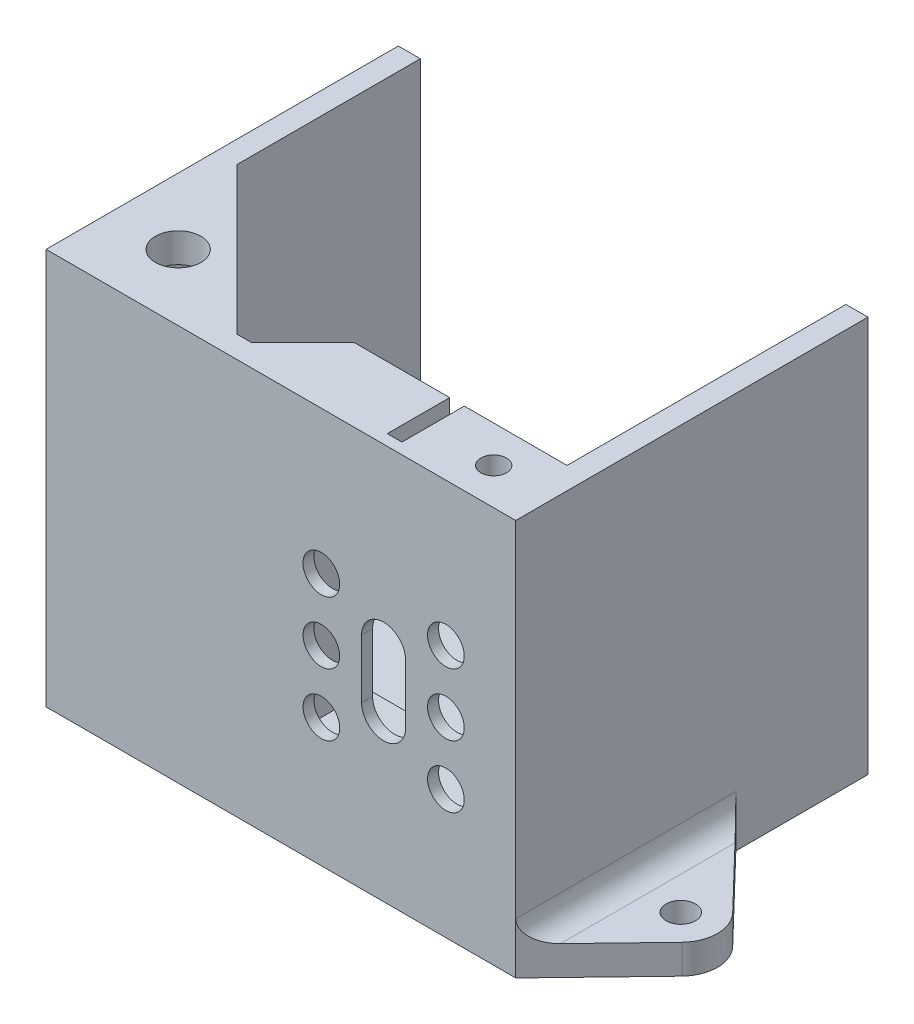
SolidWorks part; units mm, degrees
ref_plane "Płaszczyzna przednia" through (0, 0, 0) normal (0, 0, 1) x (1, 0, 0)
ref_plane "Płaszczyzna górna" through (0, 0, 0) normal (0, 1, 0) x (1, 0, 0)
ref_plane "Płaszczyzna prawa" through (0, 0, 0) normal (1, 0, 0) x (0, 0, -1)
sketch "Sketch1" plane through (0, 0, 0) normal (0, 1, 0) x (1, 0, 0)
  line L1 (-32, 24) -> (32, 24)
  line L2 (-32, 24) -> (-32, -24)
  line L3 (-32, -24) -> (32, -24)
  line L4 (32, 24) -> (32, -24)
  line L5 (-32, 24) -> (32, -24) construction
  line L6 (-32, -24) -> (32, 24) construction
  point P0 (0, 0)
  dimension "D1" = 64
  dimension "D2" = 48
extrude "Boss-Extrude1" add sketch "Sketch1" along normal blind 4
sketch "Sketch2" plane through (0, 0, 0) normal (0, -1, 0) x (1, 0, 0)
  line L9 (-20.6514, -16) -> (-22.3257, -13.1)
  line L10 (-22.3257, -13.1) -> (-25.6743, -13.1)
  line L11 (-25.6743, -13.1) -> (-27.3486, -16)
  line L12 (-27.3486, -16) -> (-25.6743, -18.9)
  line L13 (-25.6743, -18.9) -> (-22.3257, -18.9)
  line L14 (-22.3257, -18.9) -> (-20.6514, -16)
  line L15 (-32, -24) -> (-32, 24) construction
  line L16 (32, -24) -> (-32, -24) construction
  circle A0 centre (-24, -16) radius 2.9 construction
  dimension "D3" = 5.8
  dimension "D1" = 8
  dimension "D2" = 8
extrude "Cut-Extrude1" cut sketch "Sketch2" against normal blind 2.4
sketch "Sketch4" plane through (0, 0, 0) normal (0, -1, 0) x (1, 0, 0)
  line L0 (-32, -24) -> (-32, 24) construction
  line L1 (9.3486, 10) -> (7.6743, 12.9)
  line L2 (7.6743, 12.9) -> (4.3257, 12.9)
  line L3 (4.3257, 12.9) -> (2.6514, 10)
  line L4 (2.6514, 10) -> (4.3257, 7.1)
  line L5 (4.3257, 7.1) -> (7.6743, 7.1)
  line L6 (7.6743, 7.1) -> (9.3486, 10)
  line L8 (32, -24) -> (-32, -24) construction
  circle A0 centre (6, 10) radius 2.9 construction
  dimension "D3" = 5.8
  dimension "D1" = 38
  dimension "D2" = 34
extrude "Cut-Extrude2" cut sketch "Sketch4" against normal blind 2.4
sketch "Sketch6" plane through (0, 4, 0) normal (0, 1, 0) x (1, 0, 0)
  line L0 (-29, 21) -> (-29, 24)
  line L1 (-32, 24) -> (32, 24)
  line L2 (-32, 24) -> (-32, -24)
  line L3 (-32, -24) -> (32, -24)
  line L4 (32, 24) -> (32, -24)
  line L5 (-29, 21) -> (29, 21)
  line L6 (-29, 21) -> (-29, -21)
  line L7 (-29, -21) -> (29, -21)
  line L8 (29, 21) -> (29, -21)
  line L9 (-29, 21) -> (29, -21) construction
  line L10 (-29, -21) -> (29, 21) construction
  line L11 (29, 21) -> (29, 24)
  point P6 (0, 0)
  line M1 (32, -24) -> (32, 24)
  line M2 (32, 24) -> (-32, 24)
  line M3 (-32, 24) -> (-32, -24)
  line M4 (-32, -24) -> (32, -24)
  dimension "D1" = 58
  dimension "D2" = 42
extrude "Boss-Extrude3" add sketch "Sketch6" along normal blind 50 contours L11 L8 L7 L6 L0 M2 M3 M4 M1 region at (-29.8, 4, 0)
sketch "Sketch9" plane through (0, 4, 0) normal (0, 1, 0) x (1, 0, 0)
  line L0 (1, -13) -> (-7, -21)
  line L3 (29, -13) -> (1, -13)
  line L5 (-29, -21) -> (29, -21) construction
  line L6 (-7, -21) -> (29, -21)
  line L7 (1, -13) -> (-7, -21)
  line L9 (29, -21) -> (29, -13)
  line M3 (29, -21) -> (29, 24)
  line M6 (-29, -21) -> (29, -21)
  dimension "D1" = 8
  dimension "D2" = 8
  dimension "D3" = 28
extrude "Boss-Extrude4" add sketch "Sketch9" along normal blind 50 contours L3 L0 M3 M6 region at (12.9167, 4, 17.1667)
sketch "Sketch10" plane through (0, 0, 13) normal (0, 0, -1) x (-1, 0, 0)
  line L0 (-29, 54) -> (-29, 4) construction
  line L1 (-27, 39) -> (-1, 39)
  line L2 (-27, 39) -> (-27, 13)
  line L3 (-27, 13) -> (-1, 13)
  line L4 (-1, 39) -> (-1, 13)
  line L5 (-27, 39) -> (-1, 13) construction
  line L6 (-27, 13) -> (-1, 39) construction
  line L7 (-14, 39) -> (-14, 54) construction
  line L9 (-29, 54) -> (-1, 54) construction
  line L15 (-14.9986, 39) -> (-13.0014, 39)
  line L16 (-14.9986, 39) -> (-14.9986, 54)
  line L17 (-14.9986, 54) -> (-13.0014, 54)
  line L18 (-13.0014, 39) -> (-13.0014, 54)
  line L19 (-14.9986, 39) -> (-13.0014, 54) construction
  line L20 (-14.9986, 54) -> (-13.0014, 39) construction
  point P0 (-14, 26)
  point P9 (-14, 46.5)
  line M4 (-1, 4) -> (-1, 54)
  line M5 (-1, 54) -> (-29, 54)
  dimension "D1" = 26
  dimension "D2" = 26
  dimension "D3" = 15
  dimension "D5" = 28
extrude "Cut-Extrude4" cut sketch "Sketch10" against normal blind 9.5 contours L2 L3 L1 M4 | L1 M5 region at (14, 26, 13) region at (14, 46.5, 13)
sketch "Sketch13" plane through (0, 54, 0) normal (0, 1, 0) x (1, 0, 0)
  line L1 (29, -13) -> (-7.9463, -13)
  line L2 (29, -13) -> (29, -14)
  line L3 (29, -14) -> (-7.9463, -14)
  line L4 (-7.9463, -13) -> (-7.9463, -14)
  dimension "D1" = 1
extrude "Cut-Extrude6" cut sketch "Sketch13" against normal blind 32
sketch "Sketch15" plane through (0, 54, 0) normal (0, 1, 0) x (1, 0, 0)
  line L0 (-29, -1) -> (-9, -21)
  line L5 (-29, 24) -> (-29, -21) construction
  line L6 (-29, -21) -> (-7, -21) construction
  line L7 (-29, 24) -> (-29, -21) construction
  line L8 (-29, -1) -> (-29, -21)
  line L9 (-29, -21) -> (-9, -21)
  line L10 (-32, 24) -> (-32, -24) construction
  line L11 (-32, -24) -> (32, -24) construction
  circle A0 centre (-23, -15) radius 3.1
  dimension "D3" = 9
  dimension "D1" = 20
  dimension "D2" = 20
  dimension "D4" = 9
extrude "Boss-Extrude5" add sketch "Sketch15" against normal blind 4
sketch "Sketch17" plane through (0, 54, 0) normal (0, 1, 0) x (1, 0, 0)
  line L0 (32, -24) -> (32, 24) construction
  line L7 (-32, -24) -> (32, -24) construction
  line L8 (24, -19) -> (24, -24) construction
  line L9 (24, -19) -> (32, -19) construction
  line L11 (24, -15.6514) -> (21.1, -17.3257)
  line L12 (21.1, -17.3257) -> (21.1, -20.6743)
  line L13 (21.1, -20.6743) -> (24, -22.3486)
  line L14 (24, -22.3486) -> (26.9, -20.6743)
  line L15 (26.9, -20.6743) -> (26.9, -17.3257)
  line L16 (26.9, -17.3257) -> (24, -15.6514)
  circle A0 centre (24, -19) radius 2.9 construction
  dimension "D1" = 8
  dimension "D3" = 5.8
  dimension "D2" = 5
extrude "Cut-Extrude7" cut sketch "Sketch17" against normal blind 7
sketch "Sketch18" plane through (0, 0, 14) normal (0, 0, -1) x (-1, 0, 0)
  line L0 (-14.9986, 54) -> (-29, 54) construction
  line L1 (-26.9, 49.6) -> (-21.1, 49.6)
  line L2 (-26.9, 49.6) -> (-26.9, 47)
  line L3 (-26.9, 47) -> (-21.1, 47)
  line L4 (-21.1, 49.6) -> (-21.1, 47)
  line L5 (-32, 54) -> (-32, 0) construction
  point P6 (-24, 49.6)
  dimension "D1" = 7
  dimension "D2" = 2.6
  dimension "D3" = 5.8
  dimension "D4" = 8
extrude "Cut-Extrude8" cut sketch "Sketch18" against normal blind 5
sketch "Sketch19" plane through (0, 54, 0) normal (0, 1, 0) x (1, 0, 0)
  line L0 (25.75, -19) -> (22.25, -19) construction
  line L6 (22.25, -19) -> (24, -17.25) construction
  line L8 (24, -17.25) -> (24, -20.75) construction
  line L10 (20.7023, -15.4012) -> (27.2977, -15.4012)
  line L11 (20.7023, -15.4012) -> (20.7023, -22.5988)
  line L12 (20.7023, -22.5988) -> (27.2977, -22.5988)
  line L13 (27.2977, -15.4012) -> (27.2977, -22.5988)
  line L14 (20.7023, -22.5988) -> (27.2977, -22.5988)
  line L15 (20.7023, -22.5988) -> (20.7023, -15.4012)
  line L16 (20.7023, -15.4012) -> (27.2977, -15.4012)
  line L17 (27.2977, -22.5988) -> (27.2977, -15.4012)
  line L18 (20.7023, -22.5988) -> (27.2977, -15.4012) construction
  line L19 (20.7023, -15.4012) -> (27.2977, -22.5988) construction
  circle A0 centre (24, -19) radius 1.75
  line M1 (24, -15.6514) -> (26.9, -17.3257)
  line M2 (26.9, -17.3257) -> (26.9, -20.6743)
  line M3 (26.9, -20.6743) -> (24, -22.3486)
  line M4 (24, -22.3486) -> (21.1, -20.6743)
  line M5 (21.1, -20.6743) -> (21.1, -17.3257)
  line M6 (21.1, -17.3257) -> (24, -15.6514)
  dimension "D1" = 3.5
extrude "Boss-Extrude8" add sketch "Sketch19" against normal blind 4.4 contours A0 M1 M6 M5 M4 M3 M2 region at (25.4057, 54, 16.5653)
fillet "Fillet1" radius 1.5 2 edges at (-29, 50, 11) (-19, 50, 21)
sketch "Sketch20" plane through (0, 0, 0) normal (0, -1, 0) x (1, 0, 0)
  line L0 (32, 24) -> (43.1021, 12.4677)
  line L1 (39.5, 9) -> (32, 9) construction
  line L2 (32, -6) -> (43.1021, 5.5323)
  line L3 (-32, -24) -> (-42.9789, -14.5912)
  line L4 (32, -6) -> (32, 24)
  line L6 (-32, 2) -> (-32, -24)
  line L8 (-39.5, -11) -> (-32, -11) construction
  line L9 (-32, 2) -> (-42.9789, -7.4088)
  line L10 (-20.8246, -16) -> (-22.4123, -13.25) construction
  line L11 (-22.4123, -18.75) -> (-20.8246, -16) construction
  line L12 (-25.5877, -18.75) -> (-22.4123, -18.75) construction
  line L13 (-27.1754, -16) -> (-25.5877, -18.75) construction
  line L14 (-25.5877, -13.25) -> (-27.1754, -16) construction
  line L15 (-22.4123, -13.25) -> (-25.5877, -13.25) construction
  line L16 (9.1754, 10) -> (7.5877, 12.75) construction
  line L17 (7.5877, 7.25) -> (9.1754, 10) construction
  line L18 (4.4123, 7.25) -> (7.5877, 7.25) construction
  line L19 (2.8246, 10) -> (4.4123, 7.25) construction
  line L20 (4.4123, 12.75) -> (2.8246, 10) construction
  line L21 (7.5877, 12.75) -> (4.4123, 12.75) construction
  line L22 (-22.3257, -13.1) -> (-25.6743, -13.1) construction
  line L23 (-20.6514, -16) -> (-22.3257, -13.1) construction
  line L24 (-22.3257, -13.1) -> (-25.6743, -13.1) construction
  line L25 (-20.6514, -16) -> (-22.3257, -13.1) construction
  line L26 (32, -24) -> (32, 24)
  line L27 (32, 24) -> (-32, 24)
  line L28 (-32, 24) -> (-32, -24)
  line L29 (-32, -24) -> (32, -24)
  line L30 (32, -6) -> (32, 24)
  line L32 (-32, 2) -> (-32, -24)
  line L36 (9.3486, 10) -> (7.6743, 12.9)
  line L37 (7.6743, 7.1) -> (9.3486, 10)
  line L38 (4.3257, 7.1) -> (7.6743, 7.1)
  line L39 (2.6514, 10) -> (4.3257, 7.1)
  line L40 (4.3257, 12.9) -> (2.6514, 10)
  line L41 (7.6743, 12.9) -> (4.3257, 12.9)
  line L42 (9.3486, 10) -> (7.6743, 12.9) construction
  line L43 (7.6743, 7.1) -> (9.3486, 10) construction
  line L44 (4.3257, 7.1) -> (7.6743, 7.1) construction
  line L45 (2.6514, 10) -> (4.3257, 7.1) construction
  line L46 (4.3257, 12.9) -> (2.6514, 10) construction
  line L47 (7.6743, 12.9) -> (4.3257, 12.9) construction
  line L48 (-20.6514, -16) -> (-22.3257, -13.1)
  line L49 (-22.3257, -18.9) -> (-20.6514, -16)
  line L50 (-25.6743, -18.9) -> (-22.3257, -18.9)
  line L51 (-27.3486, -16) -> (-25.6743, -18.9)
  line L52 (-25.6743, -13.1) -> (-27.3486, -16)
  line L53 (-22.3257, -13.1) -> (-25.6743, -13.1)
  line L54 (-20.6514, -16) -> (-22.3257, -13.1) construction
  line L55 (-22.3257, -18.9) -> (-20.6514, -16) construction
  line L56 (-25.6743, -18.9) -> (-22.3257, -18.9) construction
  line L57 (-27.3486, -16) -> (-25.6743, -18.9) construction
  line L58 (-25.6743, -13.1) -> (-27.3486, -16) construction
  line L59 (-22.3257, -13.1) -> (-25.6743, -13.1) construction
  circle A0 centre (39.5, 9) radius 2
  circle A1 centre (-39.5, -11) radius 2
  arc A2 (43.1021, 5.5323) -> (43.1021, 12.4677) centre (39.5, 9) ccw
  arc A3 (-42.5162, -7.0122) -> (-42.5162, -14.9878) centre (-39.5, -11) ccw
  dimension "D1" = 0
  dimension "D2" = 0
  dimension "D3" = 0
extrude "Boss-Extrude9" add sketch "Sketch20" against normal blind 4 contours L9 A3 L3 L23 A1 | L2 A2 L0 L4 A0 region at (36.4432, 0, 9) region at (-36.5396, 0, -11)
fillet "Fillet2" radius 3 2 edges at (-32, 4, -11) (32, 4, 9)
sketch "Sketch22" plane through (0, 2.4, 0) normal (0, -1, 0) x (1, 0, 0)
  line L0 (4.3257, 12.9) -> (7.6743, 7.1) construction
  line L1 (7.6743, 7.1) -> (7.6743, 12.9) construction
  line L2 (7.6743, 12.9) -> (4.3257, 7.1) construction
  line L3 (-25.6743, -18.9) -> (-22.3257, -13.1) construction
  line L4 (-22.3257, -13.1) -> (-22.3257, -18.9) construction
  line L5 (-25.6743, -13.1) -> (-22.3257, -18.9) construction
  circle A0 centre (-24, -16) radius 1.75
  circle A1 centre (6, 10) radius 1.75
  dimension "D1" = 3.5
  dimension "D2" = 3.5
extrude "Cut-Extrude9" cut sketch "Sketch22" against normal blind 2
sketch "Sketch23" plane through (0, 0, 22.5) normal (0, 0, -1) x (-1, 0, 0)
  line L0 (-27, 39) -> (-1, 13) construction
  line L1 (-1, 39) -> (-27, 13) construction
  line L2 (-14, 26) -> (-14, 22) construction
  line L3 (-14, 26) -> (-14, 30) construction
  line L4 (-14, 30) -> (-14, 22) construction
  line L5 (-11, 30) -> (-11, 22)
  line L6 (-17, 30) -> (-17, 22)
  line L7 (-14, 26) -> (-1, 26) construction
  line L8 (-1, 13) -> (-1, 39) construction
  line L9 (-1, 26) -> (-27, 26) construction
  line L10 (-27, 39) -> (-27, 13) construction
  line L11 (-22.4853, 34.4853) -> (-22.4853, 17.5147) construction
  line L12 (-5.5147, 34.4853) -> (-5.5147, 17.5147) construction
  circle A1 centre (-22.4853, 34.4853) radius 2.5
  circle A2 centre (-5.5147, 34.4853) radius 2.5
  circle A3 centre (-5.5147, 17.5147) radius 2.5
  circle A4 centre (-22.4853, 17.5147) radius 2.5
  arc A6 (-11, 30) -> (-17, 30) centre (-14, 30) ccw
  arc A7 (-17, 22) -> (-11, 22) centre (-14, 22) ccw
  circle A8 centre (-22.4853, 26) radius 2.5
  circle A9 centre (-5.5147, 26) radius 2.5
  point P19 (-14, 26)
  dimension "D5" = 5
  dimension "D6" = 5
  dimension "D7" = 5
  dimension "D8" = 5
  dimension "D9" = 12
  dimension "D2" = 4
  dimension "D3" = 3
  dimension "D12" = 5
  dimension "D13" = 5
  dimension "D1" = 4
  dimension "D4" = 12
  dimension "D10" = 12
  dimension "D11" = 12
extrude "Cut-Extrude10" cut sketch "Sketch23" against normal blind 3
